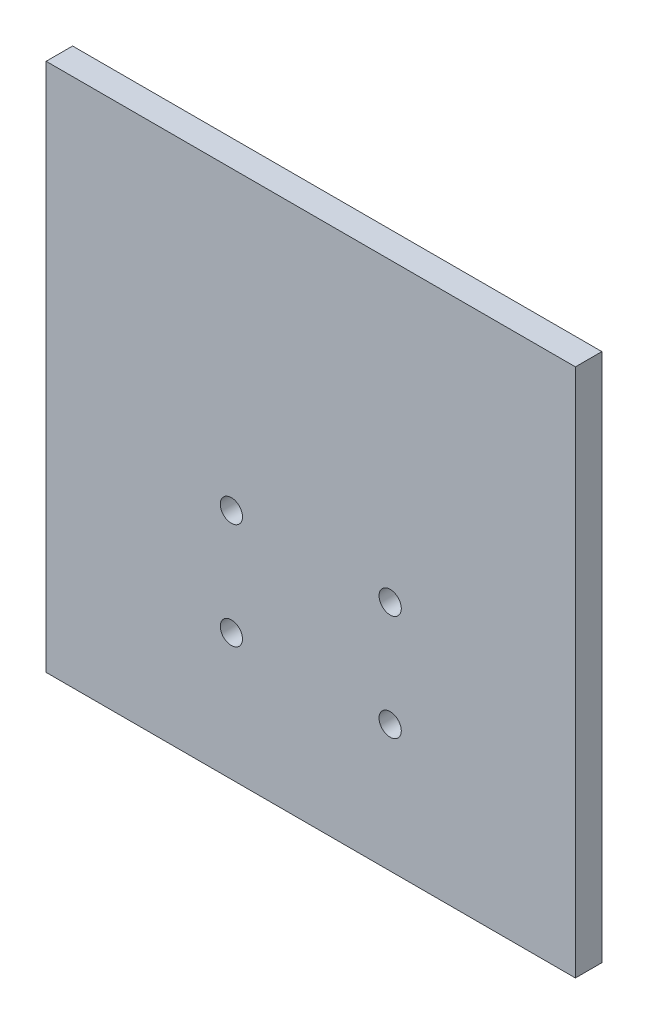
SolidWorks part; units mm, degrees
material "1060 합금"
ref_plane "정면" through (0, 0, 0) normal (0, 0, 1) x (1, 0, 0)
ref_plane "윗면" through (0, 0, 0) normal (0, 1, 0) x (1, 0, 0)
ref_plane "우측면" through (0, 0, 0) normal (1, 0, 0) x (0, 0, -1)
sketch "스케치1" plane through (0, 0, 0) normal (0, 0, 1) x (1, 0, 0)
  line L1 (-50, 50) -> (50, 50)
  line L2 (-50, 50) -> (-50, -50)
  line L3 (-50, -50) -> (50, -50)
  line L4 (50, 50) -> (50, -50)
  line L5 (-50, 50) -> (50, -50) construction
  line L6 (-50, -50) -> (50, 50) construction
  point P0 (0, 0)
  dimension "D1" = 100
  dimension "D2" = 100
extrude "보스-돌출1" add sketch "스케치1" along normal blind 5
sketch "스케치3" plane through (0, 0, 0) normal (0, 0, -1) x (-1, 0, 0)
  text T0 "front"
extrude "컷-돌출2" cut sketch "스케치3" against normal blind 0.001
ref_plane "평면1" through (0, 0, -5) normal (0, 0, -1) x (-1, 0, 0)
hole_wizard "M4x0.7 Helicoil용 탭 구멍1" positions "스케치10" profile "스케치11" tap size "M4x0.7" standard "Helicoil® Metric" end condition through all
sketch "스케치10" plane through (0, 0, -5) normal (0, 0, -1) x (-1, 0, 0)
  line L0 (50, -50) -> (-50, -50) construction
  line L1 (-50, -50) -> (-50, 50) construction
  line L2 (50, 50) -> (50, -50) construction
  point P0 (-15, -26)
  point P2 (15, -26)
  point P4 (-15, -6)
  point P6 (15, -6)
  dimension "D1" = 24
  dimension "D2" = 24
  dimension "D3" = 35
  dimension "D4" = 35
  dimension "D5" = 35
  dimension "D6" = 35
  dimension "D7" = 20
  dimension "D8" = 20
sketch "스케치11" plane through (15, -26, -5) normal (1, 0, 0) x (0, 1, 0)
  line L0 (0, 0) -> (0, 10)
  line L1 (0, 10) -> (2.1, 10)
  line L2 (2.1, 10) -> (2.1, 0)
  line L5 (2.1, 0) -> (0, 0)
  line L11 (0, -6.35) -> (0, 107.95) construction
  dimension "관통 탭 드릴 지름" = 4.2
  dimension "관통 탭 드릴 깊이" = 10
cosmetic thread "구멍 나사산1" parameters "D1"=4.7, "D2"=5.007
cosmetic thread "구멍 나사산2" parameters "D1"=4.7, "D2"=5.007
cosmetic thread "구멍 나사산3" parameters "D1"=4.7, "D2"=5.007
cosmetic thread "구멍 나사산4" parameters "D1"=4.7, "D2"=5.007
